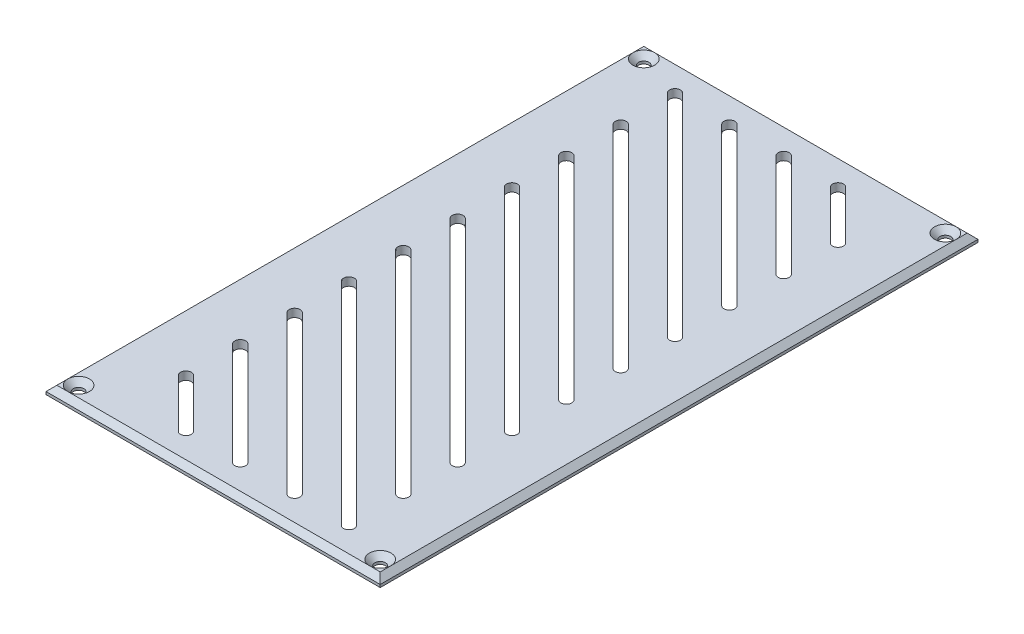
SolidWorks part; units mm, degrees
ref_plane "Front Plane" through (0, 0, 0) normal (0, 0, 1) x (1, 0, 0)
ref_plane "Top Plane" through (0, 0, 0) normal (0, 1, 0) x (1, 0, 0)
ref_plane "Right Plane" through (0, 0, 0) normal (1, 0, 0) x (0, 0, -1)
sketch "Sketch1" plane through (0, 0, 0) normal (0, 1, 0) x (1, 0, 0)
  line L1 (0, 0) -> (123, 0)
  line L2 (0, 0) -> (0, 220)
  line L3 (0, 220) -> (123, 220)
  line L4 (123, 0) -> (123, 220)
  dimension "D1" = 123
  dimension "D2" = 220
extrude "Boss-Extrude1" add sketch "Sketch1" along normal blind 4
sketch "Sketch2" plane through (0, 4, 0) normal (0, 1, 0) x (1, 0, 0)
  line L0 (0, 0) -> (123, 0) construction
  line L1 (123, 0) -> (123, 220) construction
  line L2 (123, 220) -> (0, 220) construction
  line L3 (0, 220) -> (0, 0) construction
  line L4 (0, 0) -> (123, 0)
  line L5 (123, 0) -> (123, 220)
  line L6 (123, 220) -> (0, 220)
  line L7 (0, 220) -> (0, 0)
  line L8 (4, 216) -> (4, 4)
  line L9 (4, 4) -> (119, 4)
  line L10 (119, 4) -> (119, 216)
  line L11 (119, 216) -> (4, 216)
  dimension "D1" = 4
extrude "Boss-Extrude2" add sketch "Sketch2" along normal blind 87
sketch "Sketch3" plane through (0, 0, 0) normal (0, 0, 1) x (1, 0, 0)
  line L4 (4, 4) -> (119, 4)
  line L5 (4, 91) -> (4, 4)
  line L6 (119, 91) -> (4, 91)
  line L7 (119, 4) -> (119, 91)
  line L8 (4, 4) -> (119, 4)
  line L9 (4, 49) -> (4, 4)
  line L10 (119, 49) -> (4, 49)
  line L11 (119, 4) -> (119, 49)
  dimension "D2" = 45
  dimension "D1" = 0
extrude "Cut-Extrude1" cut sketch "Sketch3" against normal up to next
sketch "Sketch4" plane through (123, 0, 0) normal (1, 0, 0) x (0, 0, -1)
  line L0 (0, 91) -> (220, 91) construction
  line L1 (50, 91) -> (200, 91)
  line L2 (50, 91) -> (50, 71)
  line L3 (50, 71) -> (200, 71)
  line L4 (200, 91) -> (200, 71)
  line L5 (220, 91) -> (220, 0) construction
  line L6 (0, 91) -> (0, 0) construction
  dimension "D1" = 20
  dimension "D2" = 20
  dimension "D3" = 50
extrude "Cut-Extrude2" cut sketch "Sketch4" against normal up to next
ref_plane "Plane1" through (0, 49, 0) normal (0, -1, 0) x (-1, 0, 0)
sketch "Sketch6" plane through (0, 49, 0) normal (0, -1, 0) x (-1, 0, 0)
  line L0 (-119, 0) -> (-119, 216) construction
  line L1 (-4, 4) -> (-119, 4) construction
  line L2 (-4, 4) -> (-4, 41)
  line L3 (-4, 41) -> (-119, 41) construction
  line L4 (-119, 4) -> (-119, 41)
  line L5 (-61.5, 41) -> (-61.5, 4) construction
  line L6 (-95, 41) -> (-95, 4)
  line L7 (-28, 41) -> (-28, 4)
  line L8 (-4, 41) -> (-28, 41)
  line L9 (-4, 4) -> (-28, 4)
  line L10 (-95, 4) -> (-119, 4)
  line L11 (-95, 41) -> (-119, 41)
  line L12 (-4, 22.5) -> (-119, 22.5) construction
  circle A0 centre (-25, 27.5) radius 1.45
  circle A1 centre (-25, 17.5) radius 1.45
  circle A2 centre (-98, 17.5) radius 1.45
  circle A3 centre (-98, 27.5) radius 1.45
  dimension "D4" = 2.9
  dimension "D1" = 37
  dimension "D5" = 3
  dimension "D6" = 5
  dimension "D2" = 33.5
  dimension "D3" = 33.5
extrude "Boss-Extrude4" add sketch "Sketch6" against normal blind 3
sketch "Sketch8" plane through (0, 91, 0) normal (0, 1, 0) x (1, 0, 0)
  line L0 (0, 110) -> (123, 110) construction
  line L1 (0, 220) -> (0, 0) construction
  line L3 (61.5, 220) -> (61.5, 0) construction
  line L4 (123, 220) -> (0, 220) construction
  line L5 (0, 0) -> (123, 0) construction
  line L6 (123, 208) -> (111, 208)
  line L7 (0, 220) -> (12, 220)
  line L8 (0, 220) -> (0, 208)
  line L9 (0, 208) -> (12, 208)
  line L10 (12, 220) -> (12, 208)
  line L11 (111, 220) -> (111, 208)
  line L12 (123, 220) -> (111, 220)
  line L13 (123, 220) -> (123, 208)
  line L14 (123, 0) -> (123, 12)
  line L15 (123, 0) -> (111, 0)
  line L16 (111, 0) -> (111, 12)
  line L17 (123, 12) -> (111, 12)
  line L18 (0, 12) -> (12, 12)
  line L19 (12, 0) -> (12, 12)
  line L20 (0, 0) -> (12, 0)
  line L21 (0, 0) -> (0, 12)
  dimension "D1" = 12
  dimension "D2" = 12
extrude "Boss-Extrude5" add sketch "Sketch8" against normal blind 10
sketch "Sketch9" plane through (0, 91, 0) normal (0, 1, 0) x (1, 0, 0)
  line L0 (0, 110) -> (123, 110) construction
  line L1 (0, 220) -> (0, 0) construction
  line L2 (123, 50) -> (123, 200) construction
  line L3 (61.5, 220) -> (61.5, 0) construction
  line L4 (123, 220) -> (0, 220) construction
  line L5 (0, 0) -> (123, 0) construction
  line L6 (12, 208) -> (12, 216) construction
  line L7 (0, 220) -> (12, 220) construction
  line L8 (0, 220) -> (0, 208) construction
  line L9 (0, 208) -> (12, 208) construction
  line L10 (12, 220) -> (12, 208) construction
  line L11 (6, 220) -> (6, 214) construction
  line L12 (6, 214) -> (12, 214) construction
  circle A0 centre (6, 214) radius 1.95
  circle A1 centre (117, 214) radius 1.95
  circle A2 centre (117, 6) radius 1.95
  circle A3 centre (6, 6) radius 1.95
  dimension "D1" = 3.9
extrude "Cut-Extrude3" cut sketch "Sketch9" against normal up to next
sketch "Sketch10" plane through (0, 0, -220) normal (0, 0, -1) x (-1, 0, 0)
  line L0 (-123, 91) -> (0, 91) construction
  line L1 (-111, 91) -> (-12, 91)
  line L2 (-111, 91) -> (-111, 51)
  line L3 (-111, 51) -> (-12, 51)
  line L4 (-12, 91) -> (-12, 51)
  dimension "D1" = 40
extrude "Cut-Extrude4" cut sketch "Sketch10" against normal up to next
chamfer "Chamfer1" distance 10 angle 45 2 edges at (119, 52, -22.5) (4, 52, -22.5)
sketch "Sketch11" plane through (0, 91, 0) normal (0, 1, 0) x (1, 0, 0)
  line L0 (0, 0) -> (123, 0) construction
  line L1 (0, 220) -> (123, 220)
  line L2 (0, 220) -> (0, 0)
  line L3 (0, 0) -> (123, 0)
  line L4 (123, 220) -> (123, 0)
  line L5 (123, 50) -> (123, 200) construction
  circle A0 centre (6, 214) radius 1.95 construction
  circle A1 centre (117, 214) radius 1.95 construction
  circle A2 centre (117, 6) radius 1.95 construction
  circle A3 centre (6, 6) radius 1.95 construction
  circle A4 centre (6, 214) radius 1.95
  circle A5 centre (117, 214) radius 1.95
  circle A6 centre (117, 6) radius 1.95
  circle A7 centre (6, 6) radius 1.95
extrude "Boss-Extrude6" add sketch "Sketch11" along normal blind 3
chamfer "Chamfer2" distance 2.05 angle 45 4 edges at (117, 94, -4.05) (6, 94, -4.05) (117, 94, -212.05) (6, 94, -212.05)
sketch "Sketch12" plane through (0, 0, -220) normal (0, 0, -1) x (-1, 0, 0)
  line L0 (0, 94) -> (0, 0) construction
  line L1 (-123, 0) -> (0, 0)
  line L2 (-123, 0) -> (-123, 91)
  line L3 (-123, 91) -> (0, 91)
  line L4 (0, 0) -> (0, 91)
  line L5 (-123, 94) -> (0, 94) construction
  dimension "D1" = 3
extrude "Cut-Extrude5" cut sketch "Sketch12" against normal through all
chamfer "Chamfer3" distance 2 angle 45 4 edges at (123, 94, -110) (61.5, 94, 0) (0, 94, -110) (61.5, 94, -220)
sketch "Sketch13" plane through (0, 94, 0) normal (0, 1, 0) x (1, 0, 0)
  line L0 (2, 110) -> (121, 110) construction
  line L1 (2, 214) -> (2, 6) construction
  line L2 (121, 6) -> (121, 214) construction
  line L3 (61.5, 218) -> (61.5, 9.4448) construction
  line L4 (117, 218) -> (6, 218) construction
  line L6 (61.5, 110) -> (22.6091, 148.8909) construction
  line L7 (61.5, 110) -> (100.3909, 71.1091) construction
  line L8 (22.6091, 148.8909) -> (100.3909, 71.1091) construction
  line L9 (24.0233, 150.3051) -> (101.8051, 72.5233)
  line L10 (21.1949, 147.4767) -> (98.9767, 69.6949)
  line L11 (22.6091, 128.8909) -> (100.3909, 51.1091) construction
  line L14 (22.6091, 108.8909) -> (100.3909, 31.1091) construction
  line L17 (22.6091, 88.8909) -> (100.3909, 11.1091) construction
  line L20 (22.6091, 68.8909) -> (80.3909, 11.1091) construction
  line L23 (22.6091, 48.8909) -> (60.3909, 11.1091) construction
  line L26 (22.6091, 28.8909) -> (40.3909, 11.1091) construction
  line L27 (24.0233, 30.3051) -> (41.8051, 12.5233)
  line L28 (21.1949, 27.4767) -> (38.9767, 9.6949)
  line L29 (22.6091, 148.8909) -> (100.3909, 71.1091) construction
  line L32 (22.6091, 128.8909) -> (100.3909, 51.1091) construction
  line L35 (22.6091, 108.8909) -> (100.3909, 31.1091) construction
  line L38 (22.6091, 88.8909) -> (100.3909, 11.1091) construction
  line L41 (22.6091, 68.8909) -> (80.3909, 11.1091) construction
  line L44 (22.6091, 48.8909) -> (60.3909, 11.1091) construction
  line L45 (24.0233, 50.3051) -> (61.8051, 12.5233)
  line L46 (21.1949, 47.4767) -> (58.9767, 9.6949)
  line L47 (22.6091, 168.8909) -> (100.3909, 91.1091) construction
  line L50 (22.6091, 148.8909) -> (100.3909, 71.1091) construction
  line L53 (22.6091, 128.8909) -> (100.3909, 51.1091) construction
  line L56 (22.6091, 108.8909) -> (100.3909, 31.1091) construction
  line L59 (22.6091, 88.8909) -> (100.3909, 11.1091) construction
  line L62 (22.6091, 68.8909) -> (80.3909, 11.1091) construction
  line L63 (24.0233, 70.3051) -> (81.8051, 12.5233)
  line L64 (21.1949, 67.4767) -> (78.9767, 9.6949)
  line L65 (22.6091, 188.8909) -> (100.3909, 111.1091) construction
  line L68 (22.6091, 168.8909) -> (100.3909, 91.1091) construction
  line L71 (22.6091, 148.8909) -> (100.3909, 71.1091) construction
  line L74 (22.6091, 128.8909) -> (100.3909, 51.1091) construction
  line L77 (22.6091, 108.8909) -> (100.3909, 31.1091) construction
  line L80 (22.6091, 88.8909) -> (100.3909, 11.1091) construction
  line L81 (24.0233, 90.3051) -> (101.8051, 12.5233)
  line L82 (21.1949, 87.4767) -> (98.9767, 9.6949)
  line L83 (22.6091, 208.8909) -> (100.3909, 131.1091) construction
  line L86 (22.6091, 188.8909) -> (100.3909, 111.1091) construction
  line L89 (22.6091, 168.8909) -> (100.3909, 91.1091) construction
  line L92 (22.6091, 148.8909) -> (100.3909, 71.1091) construction
  line L95 (22.6091, 128.8909) -> (100.3909, 51.1091) construction
  line L98 (22.6091, 108.8909) -> (100.3909, 31.1091) construction
  line L99 (24.0233, 110.3051) -> (101.8051, 32.5233)
  line L100 (21.1949, 107.4767) -> (98.9767, 29.6949)
  line L101 (42.6091, 208.8909) -> (100.3909, 151.1091) construction
  line L102 (44.0233, 210.3051) -> (101.8051, 152.5233)
  line L103 (41.1949, 207.4767) -> (98.9767, 149.6949)
  line L104 (22.6091, 208.8909) -> (100.3909, 131.1091) construction
  line L107 (22.6091, 188.8909) -> (100.3909, 111.1091) construction
  line L110 (22.6091, 168.8909) -> (100.3909, 91.1091) construction
  line L113 (22.6091, 148.8909) -> (100.3909, 71.1091) construction
  line L116 (22.6091, 128.8909) -> (100.3909, 51.1091) construction
  line L117 (24.0233, 130.3051) -> (101.8051, 52.5233)
  line L118 (21.1949, 127.4767) -> (98.9767, 49.6949)
  line L119 (62.6091, 208.8909) -> (100.3909, 171.1091) construction
  line L120 (64.0233, 210.3051) -> (101.8051, 172.5233)
  line L121 (61.1949, 207.4767) -> (98.9767, 169.6949)
  line L122 (42.6091, 208.8909) -> (100.3909, 151.1091) construction
  line L125 (22.6091, 208.8909) -> (100.3909, 131.1091) construction
  line L126 (24.0233, 210.3051) -> (101.8051, 132.5233)
  line L127 (21.1949, 207.4767) -> (98.9767, 129.6949)
  line L128 (22.6091, 188.8909) -> (100.3909, 111.1091) construction
  line L129 (24.0233, 190.3051) -> (101.8051, 112.5233)
  line L130 (21.1949, 187.4767) -> (98.9767, 109.6949)
  line L131 (22.6091, 168.8909) -> (100.3909, 91.1091) construction
  line L132 (24.0233, 170.3051) -> (101.8051, 92.5233)
  line L133 (21.1949, 167.4767) -> (98.9767, 89.6949)
  line L134 (22.6091, 148.8909) -> (100.3909, 71.1091) construction
  line L137 (22.6091, 168.8909) -> (100.3909, 91.1091) construction
  line L140 (22.6091, 188.8909) -> (100.3909, 111.1091) construction
  line L143 (22.6091, 208.8909) -> (100.3909, 131.1091) construction
  line L146 (42.6091, 208.8909) -> (100.3909, 151.1091) construction
  line L149 (62.6091, 208.8909) -> (100.3909, 171.1091) construction
  line L152 (81.1949, 210.3051) -> (100.3909, 191.1091) construction
  line L153 (84.0233, 210.3051) -> (101.8051, 192.5233)
  line L154 (81.1949, 207.4767) -> (98.9767, 189.6949)
  line L155 (22.6091, 208.8909) -> (80.6091, 208.8909) construction
  arc A0 (24.0233, 150.3051) -> (21.1949, 147.4767) centre (22.6091, 148.8909) ccw
  arc A1 (98.9767, 69.6949) -> (101.8051, 72.5233) centre (100.3909, 71.1091) ccw
  arc A2 (24.0233, 130.3051) -> (21.1949, 127.4767) centre (22.6091, 128.8909) ccw
  arc A3 (98.9767, 49.6949) -> (101.8051, 52.5233) centre (100.3909, 51.1091) ccw
  arc A4 (24.0233, 110.3051) -> (21.1949, 107.4767) centre (22.6091, 108.8909) ccw
  arc A5 (98.9767, 29.6949) -> (101.8051, 32.5233) centre (100.3909, 31.1091) ccw
  arc A6 (24.0233, 90.3051) -> (21.1949, 87.4767) centre (22.6091, 88.8909) ccw
  arc A7 (98.9767, 9.6949) -> (101.8051, 12.5233) centre (100.3909, 11.1091) ccw
  arc A8 (24.0233, 70.3051) -> (21.1949, 67.4767) centre (22.6091, 68.8909) ccw
  arc A10 (24.0233, 50.3051) -> (21.1949, 47.4767) centre (22.6091, 48.8909) ccw
  arc A12 (24.0233, 30.3051) -> (21.1949, 27.4767) centre (22.6091, 28.8909) ccw
  arc A26 (24.0233, 170.3051) -> (21.1949, 167.4767) centre (22.6091, 168.8909) ccw
  arc A27 (98.9767, 89.6949) -> (101.8051, 92.5233) centre (100.3909, 91.1091) ccw
  arc A38 (24.0233, 190.3051) -> (21.1949, 187.4767) centre (22.6091, 188.8909) ccw
  arc A39 (98.9767, 109.6949) -> (101.8051, 112.5233) centre (100.3909, 111.1091) ccw
  arc A50 (24.0233, 210.3051) -> (21.1949, 207.4767) centre (22.6091, 208.8909) ccw
  arc A51 (98.9767, 129.6949) -> (101.8051, 132.5233) centre (100.3909, 131.1091) ccw
  arc A63 (98.9767, 149.6949) -> (101.8051, 152.5233) centre (100.3909, 151.1091) ccw
  arc A75 (98.9767, 169.6949) -> (101.8051, 172.5233) centre (100.3909, 171.1091) ccw
  arc A97 (98.9767, 189.6949) -> (101.8051, 192.5233) centre (100.3909, 191.1091) ccw
  arc A98 (84.0233, 210.3051) -> (81.1949, 207.4767) centre (82.6091, 208.8909) ccw
  arc A99 (38.9767, 9.6949) -> (41.8051, 12.5233) centre (40.3909, 11.1091) ccw
  arc A100 (58.9767, 9.6949) -> (61.8051, 12.5233) centre (60.3909, 11.1091) ccw
  arc A101 (78.9767, 9.6949) -> (81.8051, 12.5233) centre (80.3909, 11.1091) ccw
  arc A111 (64.0233, 210.3051) -> (61.1949, 207.4767) centre (62.6091, 208.8909) ccw
  arc A112 (44.0233, 210.3051) -> (41.1949, 207.4767) centre (42.6091, 208.8909) ccw
  point P10 (0, 0)
  point P14 (61.5, 110)
  point P24 (61.5, 90)
  point P31 (61.5, 70)
  point P38 (61.5, 50)
  point P45 (61.5, 30)
  point P52 (61.5, 10)
  point P66 (61.5, 110)
  point P73 (61.5, 90)
  point P80 (61.5, 70)
  point P87 (61.5, 50)
  point P94 (61.5, 30)
  point P101 (61.5, 10)
  point P108 (61.5, 130)
  point P115 (61.5, 110)
  point P122 (61.5, 90)
  point P129 (61.5, 70)
  point P136 (61.5, 50)
  point P143 (61.5, 30)
  point P150 (61.5, 150)
  point P157 (61.5, 130)
  point P164 (61.5, 110)
  point P171 (61.5, 90)
  point P178 (61.5, 70)
  point P185 (61.5, 50)
  point P192 (61.5, 170)
  point P199 (61.5, 150)
  point P206 (61.5, 130)
  point P213 (61.5, 110)
  point P220 (61.5, 90)
  point P227 (61.5, 70)
  point P234 (61.5, 190)
  point P241 (61.5, 170)
  point P248 (61.5, 150)
  point P255 (61.5, 130)
  point P262 (61.5, 110)
  point P269 (61.5, 90)
  point P283 (61.5, 190)
  point P290 (61.5, 170)
  point P297 (61.5, 150)
  point P304 (61.5, 130)
  point P311 (61.5, 110)
  point P318 (61.5, 130)
  point P325 (61.5, 150)
  point P332 (61.5, 170)
  point P339 (61.5, 190)
  dimension "D1" = 45
  dimension "D2" = 45
  dimension "D3" = 55
  dimension "D4" = 55
  dimension "D5" = 4
extrude "Cut-Extrude6" cut sketch "Sketch13" against normal through all
